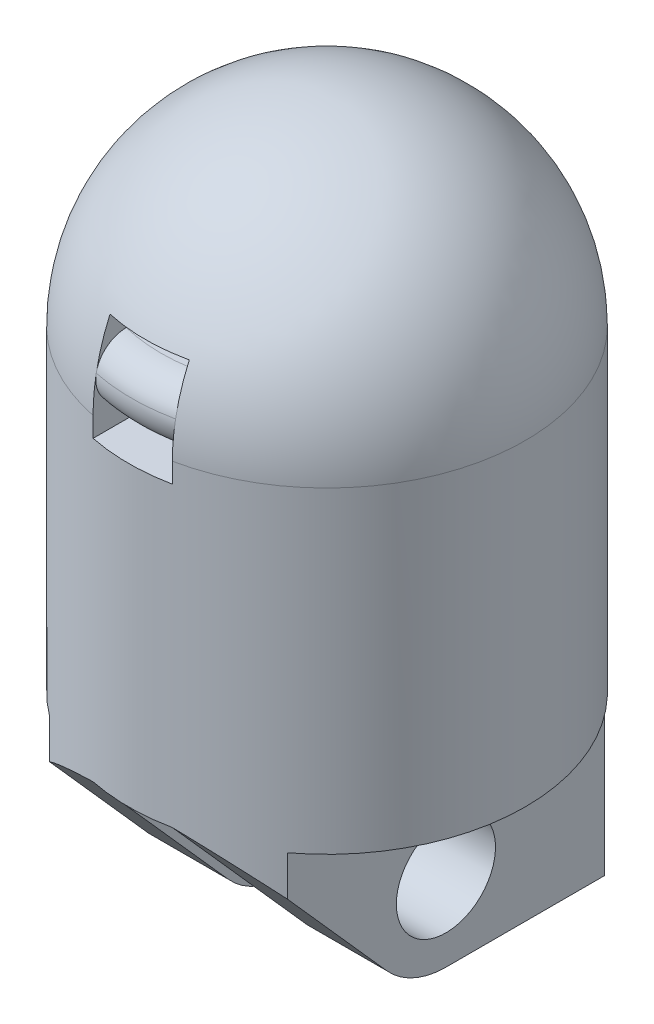
SolidWorks part; units mm, degrees
ref_plane "Front Plane" through (0, 0, 0) normal (0, 0, 1) x (1, 0, 0)
ref_plane "Top Plane" through (0, 0, 0) normal (0, 1, 0) x (1, 0, 0)
ref_plane "Right Plane" through (0, 0, 0) normal (1, 0, 0) x (0, 0, -1)
sketch "Sketch1" plane through (0, 0, 0) normal (0, 0, 1) x (1, 0, 0)
  line L0 (0, 0) -> (0, 5.6026)
  line L1 (0, 0) -> (-12.7, 0)
  line L2 (-12.7, 0) -> (-12.7, 31.75)
  line L6 (0, 5.6026) -> (-2.54, 5.6026)
  line L10 (-2.54, 36.83) -> (-2.54, 5.6026)
  line L11 (0, 36.83) -> (0, 44.45)
  line L12 (-2.54, 36.83) -> (0, 36.83)
  arc A0 (0, 44.45) -> (-12.7, 31.75) centre (0, 31.75) ccw
  dimension "D3" = 25.4
  dimension "D1" = 44.45
  dimension "D2" = 12.7
  dimension "D4" = 2.54
  dimension "D5" = 5.08
revolve "Revolve1" add sketch "Sketch1" angle 360 about L0
sketch "Sketch2" plane through (0, 0, 0) normal (0, -1, 0) x (1, 0, 0)
  line L0 (-2.54, 12.4434) -> (-2.54, -12.4434)
  line L1 (-7.62, 10.16) -> (-7.62, -10.16)
  line L2 (2.54, 12.4434) -> (2.54, -12.4434)
  line L3 (7.62, 10.16) -> (7.62, -10.16)
  circle A0 centre (0, 0) radius 12.7 construction
  arc A1 (-7.62, 10.16) -> (-7.62, -10.16) centre (0, 0) ccw
  arc A2 (-2.54, -12.4434) -> (2.54, -12.4434) centre (0, 0) ccw
  arc A3 (7.62, -10.16) -> (7.62, 10.16) centre (0, 0) ccw
  arc A4 (2.54, 12.4434) -> (-2.54, 12.4434) centre (0, 0) ccw
  dimension "D1" = 2.54
  dimension "D2" = 5.08
  dimension "D3" = 2.54
  dimension "D4" = 5.08
extrude "Cut-Extrude1" cut sketch "Sketch2" against normal blind 11.43
sketch "Sketch3" plane through (-7.62, 0, 0) normal (-1, 0, 0) x (0, 0, 1)
  line L0 (0, -55) -> (0, 55) construction
  line L1 (-10.16, 0) -> (10.16, 0) construction
  line L2 (0, 0) -> (12.4434, 0)
  line L3 (12.4434, 0) -> (12.4434, 11.43)
  line L4 (12.4434, 11.43) -> (12.4434, 0) construction
  line L5 (3.7964, 1.7046) -> (12.4434, 11.43)
  circle A0 centre (0, 5.08) radius 3.175
  arc A1 (0, 0) -> (3.7964, 1.7046) centre (0, 5.08) ccw
  dimension "D2" = 6.35
  dimension "D1" = 5.08
extrude "Cut-Extrude2" cut sketch "Sketch3" against normal through all
sketch "Sketch4" plane through (0, 0, 0) normal (0, 0, 1) x (1, 0, 0)
  line L0 (12.7, 31.75) -> (-12.7, 31.75) construction
  line L1 (-2.54, 31.75) -> (2.54, 31.75)
  line L2 (-2.54, 31.75) -> (-2.54, 30.48)
  line L3 (-2.54, 30.48) -> (2.54, 30.48)
  line L4 (2.54, 31.75) -> (2.54, 30.48)
  line L6 (-2.54, 35.56) -> (2.54, 35.56)
  line L7 (-2.54, 35.56) -> (-2.54, 36.83)
  line L8 (-2.54, 36.83) -> (2.54, 36.83)
  line L9 (2.54, 35.56) -> (2.54, 36.83)
  dimension "D1" = 1.27
  dimension "D2" = 1.27
  dimension "D3" = 3.81
extrude "Cut-Extrude3" cut sketch "Sketch4" against normal through all both and the other way through all
fillet "Fillet1" radius 1.905 4 edges at (0, 31.75, -12.7) (0, 35.56, -12.115) (0, 31.75, 12.7) (0, 35.56, 12.115)
